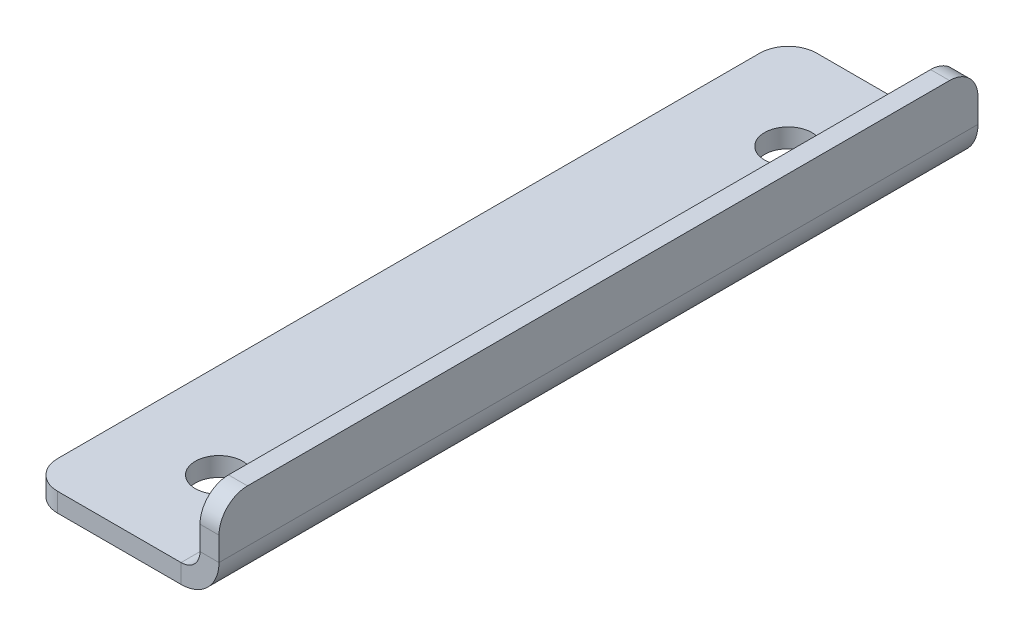
SolidWorks part; units mm, degrees
note: The reader was unsure of these and kept them because the rebuilt part matched: flange length of "Edge-Flange1".
ref_plane "Front Plane" through (0, 0, 0) normal (0, 0, 1) x (1, 0, 0)
ref_plane "Top Plane" through (0, 0, 0) normal (0, 1, 0) x (1, 0, 0)
ref_plane "Right Plane" through (0, 0, 0) normal (1, 0, 0) x (0, 0, -1)
sketch "Sketch1" plane through (0, 0, 0) normal (0, 1, 0) x (1, 0, 0)
  line L1 (10, -40) -> (-10, -40)
  line L2 (10, -40) -> (10, 40)
  line L3 (10, 40) -> (-10, 40)
  line L4 (-10, -40) -> (-10, 40)
  line L5 (10, -40) -> (-10, 40) construction
  line L6 (10, 40) -> (-10, -40) construction
  point P0 (0, 0)
  dimension "D1" = 80
  dimension "D2" = 20
base flange "Base-Flange1" sketch "Sketch1" thickness 2 reverse thickness direction yes parameters "D1"=9
edge flange "Edge-Flange1" sketch "Sketch8" flange angle 90 flange length 9.5 flange position material inside bend radius 2 thickness 2 relief rectangular parameters "D6"=10
sketch "Sketch8" plane through (10, 2, 0) normal (-1, 0, 0) x (0, 0, 1)
  line L2 (-40, 0) -> (-40, 7.5)
  line L3 (-40, 7.5) -> (40, 7.5)
  line L4 (40, 7.5) -> (40, 0)
  line L5 (40, 0) -> (-40, 0) construction
  line L6 (40, 0) -> (-40, 0)
bend "EdgeBend1" bend radius 2 bend angle 90 parameters "D5"=1
sketch "Sketch11" plane through (0, 2, 0) normal (0, 1, 0) x (1, 0, 0)
  line L0 (6, 40) -> (-10, 40) construction
  line L1 (-10, 40) -> (-10, -40) construction
  line L2 (-10, -40) -> (6, -40) construction
  point P0 (0, 30)
  point P2 (0, -30)
  dimension "D1" = 10
  dimension "D2" = 10
  dimension "D3" = 10
  dimension "D4" = 10
hole_wizard "Ø5.0mm Dowel Hole1" positions "Sketch11" profile "Sketch10" hole size "Ø5.0" standard "ISO" end condition through all
sketch "Sketch10" plane through (0, 2, -30) normal (1, 0, 0) x (0, 0, 1)
  line L0 (0, 0) -> (0, 2)
  line L1 (0, 2) -> (2.5, 2)
  line L2 (2.5, 2) -> (2.5, 0)
  line L5 (2.5, 0) -> (0, 0)
  line L11 (0, -6.35) -> (0, 107.95) construction
  dimension "Thru Hole Dia." = 5
  dimension "Thru Hole Depth" = 2
fillet "Fillet1" radius 3 4 edges at (-10, 1, -40) (9, 9.5, -40) (-10, 1, 40) (9, 9.5, 40)
sketch "Bend-Lines1" [suppressed] plane through (0, 0, 0) normal (0, 1, 0) x (1, 0, 0)
sketch "Bounding-Box1" [suppressed] plane through (0, 0, 0) normal (0, 1, 0) x (1, 0, 0)
sheet metal parameters "Sheet-Metal1" thickness 2 parameters "D1"=9
flat pattern "Flat-Pattern1" [suppressed]
sketch "Bend-Lines2" plane through (0, 0, 0) normal (0, 1, 0) x (1, 0, 0)
sketch3d "Bounding-Box2" [suppressed]
  line L0 (-10, 40, 0) -> (-10, -40, 0) construction
  line L1 (10, 40, 0) -> (10, -40, 0) construction
  line L2 (-10, 40, 0) -> (10, 40, 0) construction
  line L3 (-10, -40, 0) -> (10, -40, 0) construction
sheet metal parameters "Sheet-Metal2" thickness 2 parameters "D1"=9
flat pattern "Flat-Pattern1"
sketch "Bend-Lines2" plane through (0, 0, 0) normal (0, -1, 0) x (-1, 0, 0)
  line L0 (-8.3562, 40) -> (-8.3562, -40) construction
  line L1 (-8.3562, 40) -> (-8.3562, -40) construction
sketch3d "Bounding-Box2" [suppressed]
  line L0 (10, 40, 0) -> (10, -40, 0) construction
  line L1 (-16.2124, 40, 0) -> (-16.2124, -40, 0) construction
  line L2 (10, 40, 0) -> (-16.2124, 40, 0) construction
  line L3 (10, -40, 0) -> (-16.2124, -40, 0) construction
bend of the flat pattern "Flatten-<EdgeBend1>1"
sheet metal parameters "Sheet-Metal3" thickness 2 parameters "D1"=9
flat pattern "Flat-Pattern1"
sketch "Bend-Lines2" plane through (0, 0, 0) normal (0, -1, 0) x (-1, 0, 0)
  line L0 (-8.3562, 40) -> (-8.3562, -40) construction
  line L1 (-8.3562, 40) -> (-8.3562, -40) construction
sketch3d "Bounding-Box2" [suppressed]
  line L0 (10, 40, 0) -> (10, -40, 0) construction
  line L1 (-16.2124, 40, 0) -> (-16.2124, -40, 0) construction
  line L2 (10, 40, 0) -> (-16.2124, 40, 0) construction
  line L3 (10, -40, 0) -> (-16.2124, -40, 0) construction
bend of the flat pattern "Flatten-<EdgeBend1>1"
